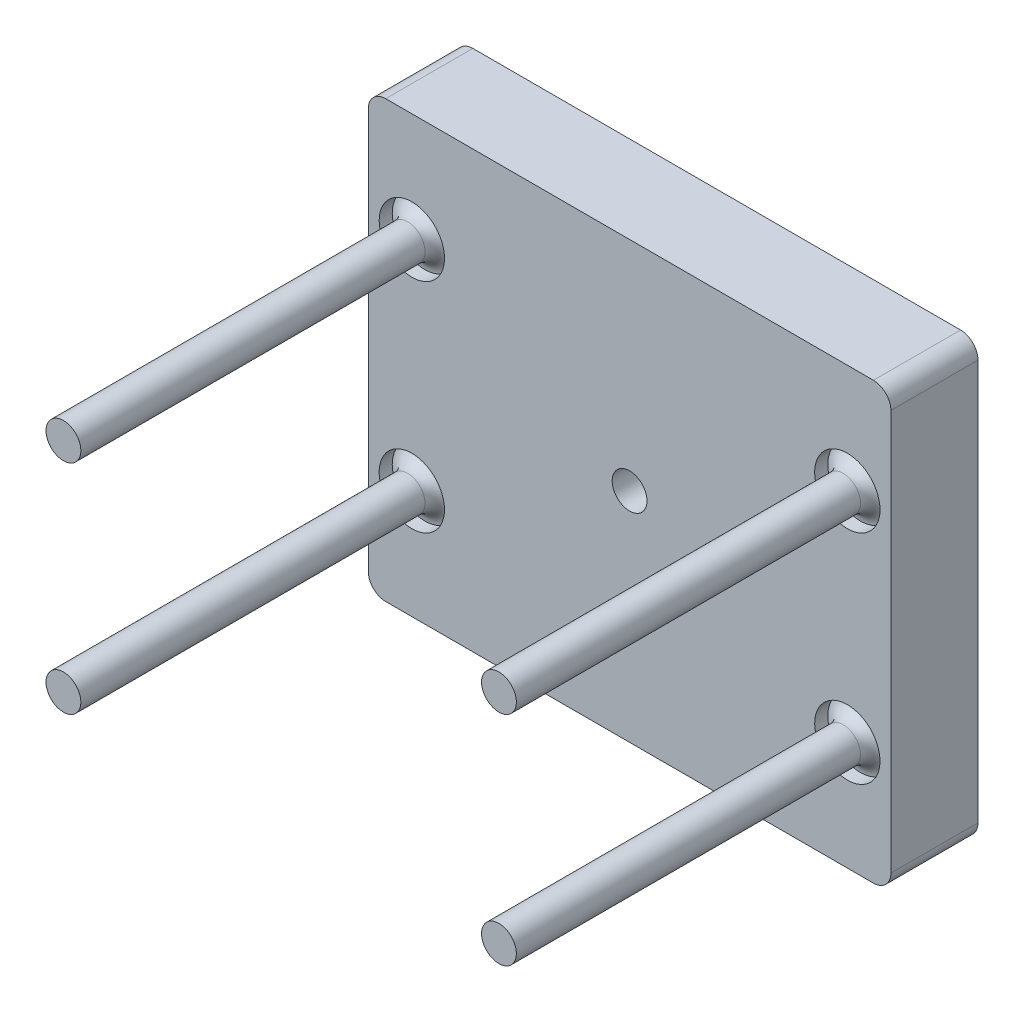
SolidWorks part; units mm, degrees
ref_plane "Plan de face" through (0, 0, 0) normal (0, 0, 1) x (1, 0, 0)
ref_plane "Plan de dessus" through (0, 0, 0) normal (0, 1, 0) x (1, 0, 0)
ref_plane "Plan de droite" through (0, 0, 0) normal (1, 0, 0) x (0, 0, -1)
sketch "Esquisse1" plane through (0, 0, 0) normal (0, 0, 1) x (1, 0, 0)
  line L1 (0, 0) -> (60, 0)
  line L2 (0, 0) -> (0, -50)
  line L3 (0, -50) -> (60, -50)
  line L4 (60, 0) -> (60, -50)
  dimension "D1" = 60
  dimension "D2" = 50
extrude "Boss.-Extru.1" add sketch "Esquisse1" along normal mid plane 10
sketch "Esquisse2" plane through (0, 0, 5) normal (0, 0, 1) x (1, 0, 0)
  line L0 (30, 0) -> (30, -50) construction
  line L1 (60, 0) -> (0, 0) construction
  line L2 (0, -50) -> (60, -50) construction
  line L3 (0, -25) -> (60, -25) construction
  line L4 (0, 0) -> (0, -50) construction
  line L5 (60, -50) -> (60, 0) construction
  circle A0 centre (5, -12.5) radius 2
  circle A1 centre (5, -37.5) radius 2
  circle A2 centre (55, -37.5) radius 2
  circle A3 centre (55, -12.5) radius 2
  dimension "D1" = 4
  dimension "D2" = 12.5
  dimension "D3" = 25
extrude "Boss.-Extru.2" add sketch "Esquisse2" along normal blind 40
sketch "Esquisse3" plane through (0, 0, 5) normal (0, 0, 1) x (1, 0, 0)
  circle A0 centre (30, -25) radius 2
  dimension "D1" = 4
extrude "Enlèv. mat.-Extru.1" cut sketch "Esquisse3" against normal through all
fillet "Congé1" radius 2 1 edges at (0, 0, 0)
fillet "Congé2" radius 2 3 edges at (0, -50, 0) (60, -50, 0) (60, 0, 0)
sketch "Esquisse4" plane through (0, 0, 5) normal (0, 0, 1) x (1, 0, 0)
  line L0 (60, -25) -> (0, -25) construction
  line L1 (60, -48) -> (60, -2) construction
  line L2 (0, -2) -> (0, -48) construction
  line L3 (30, -50) -> (30, 0) construction
  line L4 (2, -50) -> (58, -50) construction
  line L5 (58, 0) -> (2, 0) construction
  circle A0 centre (5, -37.5) radius 3.75
  circle A1 centre (5, -12.5) radius 3.75
  circle A2 centre (55, -12.5) radius 3.75
  circle A3 centre (55, -37.5) radius 3.75
  circle A4 centre (55, -37.5) radius 2
  circle A5 centre (5, -37.5) radius 2
  circle A6 centre (5, -12.5) radius 2
  circle A7 centre (55, -12.5) radius 2
  dimension "D1" = 7.5
extrude "Enlèv. mat.-Extru.5" cut sketch "Esquisse4" against normal blind 1.5
fillet "Congé5" radius 2 1 edges at (57, -37.5, 3.5)
fillet "Congé6" radius 2 1 edges at (57, -12.5, 3.5)
fillet "Congé7" radius 2 1 edges at (7, -12.5, 3.5)
fillet "Congé8" radius 2 1 edges at (7, -37.5, 3.5)
